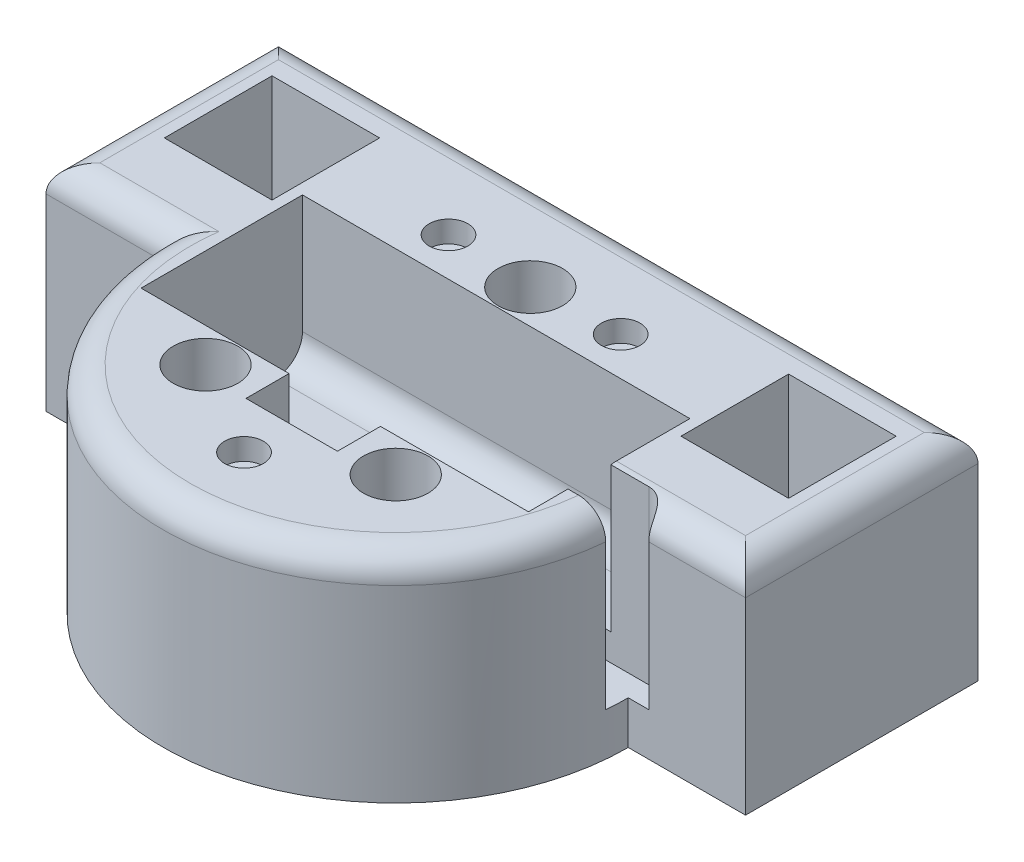
SolidWorks part; units mm, degrees
ref_plane "Front Plane" through (0, 0, 0) normal (0, 0, 1) x (1, 0, 0)
ref_plane "Top Plane" through (0, 0, 0) normal (0, 1, 0) x (1, 0, 0)
ref_plane "Right Plane" through (0, 0, 0) normal (1, 0, 0) x (0, 0, -1)
sketch "Sketch1" plane through (0, 0, 0) normal (0, 1, 0) x (1, 0, 0)
  line L0 (-65, 43.2) -> (65, 43.2)
  line L1 (43.2, 0) -> (65, 0)
  line L2 (65, 0) -> (65, 43.2)
  line L3 (-43.2, 0) -> (-65, 0)
  line L4 (-65, 0) -> (-65, 43.2)
  circle A0 centre (0, 0) radius 25 construction
  circle A1 centre (0, 0) radius 43.2
  point P6 (0, 43.2)
  dimension "D1" = 86.4
  dimension "D2" = 50
  dimension "D3" = 130
extrude "Boss-Extrude1" add sketch "Sketch1" along normal blind 40 contours A1 | A1 L0 L4 L3 | A1 L1 L2 L0 region at (-47.9685, 0, -25.1658) region at (47.9685, 0, -25.1658) region at (0, 0, 0)
sketch "Sketch2" plane through (0, 40, 0) normal (0, 1, 0) x (1, 0, 0)
  line L0 (65, 25) -> (48, 25) construction
  line L1 (65, 0) -> (65, 43.2) construction
  line L2 (48, 25) -> (48, 43.2) construction
  line L3 (-65, 43.2) -> (65, 43.2) construction
  line L4 (-65, 25) -> (-48, 25) construction
  line L6 (-48, 25) -> (-48, 43.2) construction
  line L8 (38, 15) -> (58, 15)
  line L9 (38, 15) -> (38, 35)
  line L10 (38, 35) -> (58, 35)
  line L11 (58, 15) -> (58, 35)
  line L12 (38, 15) -> (58, 35) construction
  line L13 (38, 35) -> (58, 15) construction
  line L14 (-58, 15) -> (-38, 15)
  line L15 (-58, 15) -> (-58, 35)
  line L16 (-58, 35) -> (-38, 35)
  line L17 (-38, 15) -> (-38, 35)
  line L18 (-58, 15) -> (-38, 35) construction
  line L19 (-58, 35) -> (-38, 15) construction
  circle A0 centre (0, 0) radius 25 construction
  circle A1 centre (0, 25) radius 3
  circle A10 centre (0, 0) radius 25 construction
  circle A12 centre (0, 0) radius 25 construction
  circle A13 centre (17.6777, -17.6777) radius 3
  circle A14 centre (0, 0) radius 25 construction
  circle A16 centre (0, 0) radius 25 construction
  circle A17 centre (-17.6777, -17.6777) radius 3
  circle A18 centre (0, 0) radius 25 construction
  circle A20 centre (0, 0) radius 25 construction
  circle A22 centre (0, 0) radius 25 construction
  arc A23 (2.9946, -24.82) -> (-2.9946, -24.82) centre (0, -25) ccw [skipped]
  arc A24 (24.82, -2.9946) -> (24.82, 2.9946) centre (25, 0) ccw [skipped]
  arc A25 (-24.82, 2.9946) -> (-24.82, -2.9946) centre (-25, 0) ccw [skipped]
  arc A26 (-19.6679, 15.4329) -> (-15.4329, 19.6679) centre (-17.6777, 17.6777) ccw [skipped]
  arc A27 (19.6679, 15.4329) -> (15.4329, 19.6679) centre (17.6777, 17.6777) ccw [skipped]
  point P21 (0, -12.5)
  point P30 (0, 0)
  point P53 (0, 0)
  point P54 (0, 0)
  dimension "D1" = 8
  dimension "D2" = 50
  dimension "D3" = 6
  dimension "D4" = 17
  dimension "D5" = 20
  dimension "D6" = 20
extrude "Cut-Extrude1" cut sketch "Sketch2" against normal blind 50
sketch "Sketch3" plane through (0, 40, 0) normal (0, 1, 0) x (1, 0, 0)
  line L0 (0, -11.3388) -> (0, -19.3388)
  line L1 (-36, -11.3388) -> (36, -11.3388)
  line L2 (-36, -11.3388) -> (-36, 18.6612)
  line L3 (-36, 18.6612) -> (36, 18.6612)
  line L4 (36, -11.3388) -> (36, 18.6612)
  line L5 (-36, 3.6612) -> (36, 3.6612) construction
  line L6 (0, 3.6612) -> (0, -43.2) construction
  line L7 (0, -19.3388) -> (8.5, -19.3388)
  line L8 (8.5, -19.3388) -> (8.5, -11.3388)
  line L9 (0, -19.3388) -> (-8.5, -19.3388)
  line L10 (-8.5, -19.3388) -> (-8.5, -11.3388)
  line L11 (0, 25) -> (0, 18.6612) construction
  line L12 (17.6777, -17.6777) -> (17.6777, -11.3388) construction
  circle A1 centre (0, 0) radius 43.2 construction
  dimension "D1" = 8
  dimension "D2" = 8.5
  dimension "D3" = 72
  dimension "D4" = 30
  dimension "D5" = 6.3388
extrude "Cut-Extrude2" cut sketch "Sketch3" against normal blind 27 contours L7 L8 L1 L0 | L10 L9 L0 L1 | L1 L4 L3 L2 region at (4.25, 40, 15.3388) region at (-4.25, 40, 15.3388) region at (0, 40, -3.6612)
fillet "Fillet1" radius 5 3 edges at (0, 13, -18.6612) (22.25, 13, 11.3388) (-22.25, 13, 11.3388)
sketch "Sketch4" plane through (0, 40, 0) normal (0, 1, 0) x (1, 0, 0)
  line L3 (23.0144, 4) -> (43.0144, 4)
  line L4 (23.0144, -4) -> (43.0144, -4)
  circle A1 centre (23.0144, 0) radius 4
  circle A2 centre (0, 0) radius 43.2 construction
  arc A3 (43.0144, 4) -> (43.0144, -4) centre (43.0144, 0) cw
  dimension "D1" = 8
  dimension "D2" = 20
extrude "Cut-Extrude3" cut sketch "Sketch4" against normal blind 32 contours L4 L3 | A1 L4 L3 | A1 | A3 region at (36.156, 40, 0) region at (23.0144, 40, 0)
sketch "Sketch5" plane through (0, 40, 0) normal (0, 1, 0) x (1, 0, 0)
  line L0 (-36, -12.2) -> (-36, -20.2) construction
  line L1 (-36, -20.2) -> (36, -20.2) construction
  line L2 (36, -20.2) -> (36, -12.2) construction
  line L3 (-36, -12.2) -> (36, -12.2) construction
  line L4 (-36, 17.8) -> (-36, 25.8) construction
  line L5 (-36, 25.8) -> (36, 25.8) construction
  line L6 (36, 25.8) -> (36, 17.8) construction
  line L7 (36, 17.8) -> (-36, 17.8) construction
  line L8 (-16, 25.8) -> (-16, 17.8) construction
  line L9 (16, 25.8) -> (16, 17.8) construction
  line L10 (-16, -12.2) -> (-16, -20.2) construction
  line L11 (16, -12.2) -> (16, -20.2) construction
  line L12 (36, 17.8) -> (36, -12.2) construction
  line L13 (0, -12.2) -> (0, -43.2) construction
  line L14 (-8.5, -28.2) -> (8.5, -28.2) construction
  circle A2 centre (16, 25.8) radius 3.6
  circle A3 centre (-16, 25.8) radius 3.6
  arc A4 (43.0144, 4) -> (43.0144, -4) centre (0, 0) ccw construction
  circle A5 centre (0, -28.2) radius 3.6
  dimension "D7" = 7.2
  dimension "D8" = 8
  dimension "D1" = 8
  dimension "D2" = 8
  dimension "D3" = 20
  dimension "D4" = 20
  dimension "D5" = 20
  dimension "D6" = 20
extrude "Cut-Extrude4" cut sketch "Sketch5" against normal blind 4
fillet "Fillet3" radius 5 6 edges at (-2.0022, 40, 43.1536) (56.0072, 40, 0) (-54.1, 40, 0) (-65, 40, -21.6) (65, 40, -21.6) (0, 40, -43.2)
sketch "Sketch7" plane through (0, 40, 0) normal (0, 1, 0) x (1, 0, 0)
  line L0 (-36, 18.6612) -> (36, 18.6612) construction
  line L1 (8.5, -11.3388) -> (36, -11.3388) construction
  circle A0 centre (0, 25) radius 6
  circle A1 centre (17.6777, -17.6777) radius 6
  circle A2 centre (-17.6777, -17.6777) radius 6
  dimension "D1" = 12
  dimension "D2" = 6.3388
  dimension "D3" = 6.3388
extrude "Cut-Extrude5" cut sketch "Sketch7" against normal blind 36 from offset 0
